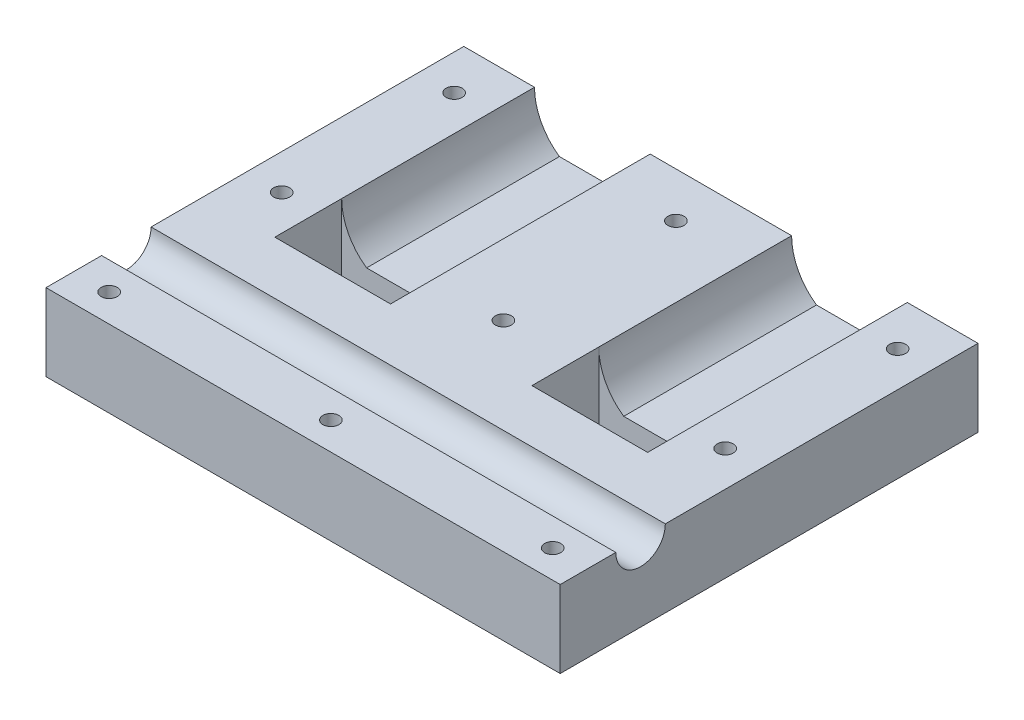
SolidWorks part; units mm, degrees
ref_plane "Front Plane" through (0, 0, 0) normal (0, 0, 1) x (1, 0, 0)
ref_plane "Top Plane" through (0, 0, 0) normal (0, 1, 0) x (1, 0, 0)
ref_plane "Right Plane" through (0, 0, 0) normal (1, 0, 0) x (0, 0, -1)
sketch "Sketch1" plane through (0, 0, 0) normal (0, 0, 1) x (1, 0, 0)
  line L0 (-50.8, 0) -> (50.8, 0)
  line L1 (50.8, 0) -> (50.8, 15.24)
  line L2 (50.8, 15.24) -> (36.83, 15.24)
  line L3 (25.4, 15.24) -> (51.7323, 15.24) construction
  line L4 (13.97, 15.24) -> (-13.97, 15.24)
  line L5 (31.9056, 5.842) -> (18.8944, 5.842)
  line L6 (0, 0) -> (0, 35.6145) construction
  line L7 (-25.4, 15.24) -> (-51.7323, 15.24) construction
  line L8 (-31.9056, 5.842) -> (-18.8944, 5.842)
  line L9 (-50.8, 15.24) -> (-36.83, 15.24)
  line L10 (-50.8, 0) -> (-50.8, 15.24)
  arc A0 (13.97, 15.24) -> (18.8944, 5.842) centre (25.4, 15.24) ccw
  arc A1 (31.9056, 5.842) -> (36.83, 15.24) centre (25.4, 15.24) ccw
  arc A2 (-31.9056, 5.842) -> (-36.83, 15.24) centre (-25.4, 15.24) cw
  arc A3 (-13.97, 15.24) -> (-18.8944, 5.842) centre (-25.4, 15.24) cw
  point P13 (43.815, 15.24)
  point P20 (0, 15.24)
  point P23 (-43.815, 15.24)
  dimension "D1" = 22.86
  dimension "D2" = 9.398
  dimension "D3" = 15.24
  dimension "D4" = 25.4
  dimension "D5" = 50.8
extrude "Boss-Extrude1" add sketch "Sketch1" along normal blind 38.1
hole_wizard "Hole2" positions "Sketch4" profile "Sketch5" legacy
sketch "Sketch4" plane through (0, 15.24, 0) normal (0, 1, 0) x (1, 0, 0)
  point P0 (-43.815, -8.89)
  dimension "D2" = 8.89
sketch "Sketch5" plane through (-43.815, 15.24, 8.89) normal (1, 0, 0) x (0, 0, 1)
  line L0 (0, 0) -> (0, 100)
  line L1 (0, 100) -> (1.5875, 99.0461)
  line L2 (1.5875, 99.0461) -> (1.5875, 0)
  line L4 (1.5875, 0) -> (0, 0)
  line L6 (0, 100) -> (-1.5875, 99.0461) construction
  line L7 (0, -4.2442) -> (0, 117.3081) construction
  dimension "Diameter" = 3.175
  dimension "Depth" = 100
  dimension "Drill Angle" = 118
sketch "Sketch7" plane through (0, 0, 38.1) normal (0, 0, 1) x (1, 0, 0)
  line L1 (-50.8, 15.24) -> (50.8, 15.24)
  line L2 (-50.8, 15.24) -> (-50.8, 0)
  line L3 (-50.8, 0) -> (50.8, 0)
  line L4 (50.8, 15.24) -> (50.8, 0)
extrude "Boss-Extrude2" add sketch "Sketch7" along normal blind 44.45
sketch "Sketch8" plane through (0, 15.24, 0) normal (0, 1, 0) x (1, 0, 0)
  line L0 (0, 0) -> (0, -81.5203) construction
  line L1 (-13.97, -38.1) -> (-13.97, 0) construction
  line L2 (-36.83, -38.1) -> (-13.97, -38.1)
  line L3 (-36.83, -38.1) -> (-36.83, -51.308)
  line L4 (-36.83, -51.308) -> (-13.97, -51.308)
  line L5 (-13.97, -38.1) -> (-13.97, -51.308)
  line L6 (13.97, -38.1) -> (13.97, -51.308)
  line L7 (36.83, -51.308) -> (13.97, -51.308)
  line L8 (36.83, -38.1) -> (36.83, -51.308)
  line L9 (36.83, -38.1) -> (13.97, -38.1)
  dimension "D1" = 13.208
extrude "Cut-Extrude1" cut sketch "Sketch8" against normal up to surface (15.24 mm away) up to face at (-43.815, 0, 10.4775)
sketch "Sketch9" plane through (-50.8, 0, 0) normal (-1, 0, 0) x (0, 0, 1)
  line L0 (82.55, 15.24) -> (0, 15.24) construction
  line L2 (0, 15.24) -> (0, 0) construction
  line L3 (82.55, 15.24) -> (71.5645, 15.24) construction
  line L4 (38.1, 15.24) -> (51.308, 15.24) construction
  line L5 (38.1, 15.24) -> (51.308, 15.24) construction
  circle A0 centre (66.675, 15.24) radius 4.8895
  point P11 (44.704, 15.24)
  point P12 (77.0572, 15.24)
  dimension "D2" = 9.779
  dimension "D1" = 66.675
extrude "Cut-Extrude2" cut sketch "Sketch9" against normal up to surface (101.6 mm away) up to face at (50.8, 7.62, 41.275)
pattern_linear "LPattern1" count 3 spacing 34.0836 along (0, 0, 1) count 3 spacing 43.815 along (1, 0, 0) of "Hole2"
